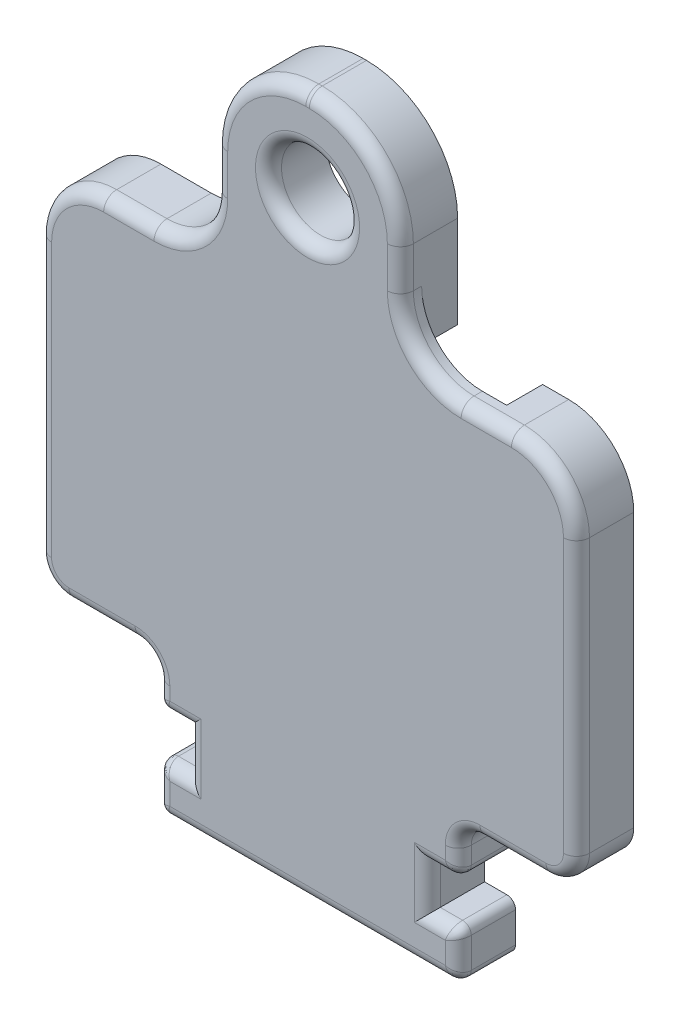
SolidWorks part; units mm, degrees
ref_plane "Front Plane" through (0, 0, 0) normal (0, 0, 1) x (1, 0, 0)
ref_plane "Top Plane" through (0, 0, 0) normal (0, 1, 0) x (1, 0, 0)
ref_plane "Right Plane" through (0, 0, 0) normal (1, 0, 0) x (0, 0, -1)
sketch "Sketch1" plane through (0, 0, 0) normal (0, 0, 1) x (1, 0, 0)
  line L0 (-8.8265, -16.637) -> (-8.8265, -18.415)
  line L1 (-11.938, 10.795) -> (-8.9916, 10.795)
  line L2 (-15.748, 6.985) -> (-15.748, -9.017)
  line L3 (-13.97, -10.795) -> (-10.0965, -10.795)
  line L4 (-8.3185, -13.589) -> (-7.0104, -13.589)
  line L5 (8.8265, -12.065) -> (8.8265, -13.081)
  line L6 (0, 22.0726) -> (0, -18.923) construction
  line L7 (-0.1016, 22.0726) -> (0.1016, 22.0726)
  line L8 (-5.4356, 16.7386) -> (-5.4356, 14.351)
  line L9 (-8.3185, -16.129) -> (-7.0104, -16.129)
  line L10 (-7.0104, -13.589) -> (-7.0104, -16.129)
  line L11 (7.0104, -13.589) -> (7.0104, -16.129)
  line L12 (8.3185, -16.129) -> (7.0104, -16.129)
  line L13 (5.4356, 16.7386) -> (5.4356, 14.351)
  line L14 (-8.8265, -12.065) -> (-8.8265, -13.081)
  line L15 (-8.3185, -18.923) -> (8.3185, -18.923)
  line L16 (8.3185, -13.589) -> (7.0104, -13.589)
  line L17 (13.97, -10.795) -> (10.0965, -10.795)
  line L18 (15.748, 6.985) -> (15.748, -9.017)
  line L19 (11.938, 10.795) -> (8.9916, 10.795)
  line L20 (8.8265, -16.637) -> (8.8265, -18.415)
  arc A0 (-0.1016, 22.0726) -> (-5.4356, 16.7386) centre (-0.1016, 16.7386) ccw
  arc A1 (-5.4356, 14.351) -> (-8.9916, 10.795) centre (-8.9916, 14.351) cw
  arc A2 (-11.938, 10.795) -> (-15.748, 6.985) centre (-11.938, 6.985) ccw
  arc A3 (-15.748, -9.017) -> (-13.97, -10.795) centre (-13.97, -9.017) ccw
  arc A4 (-8.8265, -12.065) -> (-10.0965, -10.795) centre (-10.0965, -12.065) ccw
  arc A5 (-8.3185, -13.589) -> (-8.8265, -13.081) centre (-8.3185, -13.081) cw
  arc A6 (-8.3185, -16.129) -> (-8.8265, -16.637) centre (-8.3185, -16.637) ccw
  arc A7 (-8.8265, -18.415) -> (-8.3185, -18.923) centre (-8.3185, -18.415) ccw
  circle A8 centre (0, 16.7386) radius 2.286
  arc A9 (8.8265, -18.415) -> (8.3185, -18.923) centre (8.3185, -18.415) cw
  arc A10 (8.3185, -16.129) -> (8.8265, -16.637) centre (8.3185, -16.637) cw
  arc A11 (8.3185, -13.589) -> (8.8265, -13.081) centre (8.3185, -13.081) ccw
  arc A12 (8.8265, -12.065) -> (10.0965, -10.795) centre (10.0965, -12.065) cw
  arc A13 (15.748, -9.017) -> (13.97, -10.795) centre (13.97, -9.017) cw
  arc A14 (11.938, 10.795) -> (15.748, 6.985) centre (11.938, 6.985) cw
  arc A15 (5.4356, 14.351) -> (8.9916, 10.795) centre (8.9916, 14.351) ccw
  arc A16 (0.1016, 22.0726) -> (5.4356, 16.7386) centre (0.1016, 16.7386) cw
  point P0 (0, 0)
  point P1 (-8.8265, -14.859)
  point P6 (0, 10.795)
  point P11 (0, -10.795)
  point P17 (-7.0104, -14.859)
  point P20 (-5.4356, 22.0726)
  point P23 (-5.4356, 10.795)
  point P26 (-15.748, 10.795)
  point P29 (-15.748, -10.795)
  point P32 (-8.8265, -10.795)
  point P37 (-8.8265, -16.129)
  point P40 (-8.8265, -18.923)
  point P67 (8.8265, -14.859)
  point P70 (0, 1.5748)
  dimension "D9" = 5.334
  dimension "D10" = 3.556
  dimension "D11" = 3.81
  dimension "D12" = 1.778
  dimension "D13" = 1.27
  dimension "D14" = 0.508
  dimension "D15" = 0.508
  dimension "D16" = 0.508
  dimension "D17" = 5.334
  dimension "D1" = 8.8265
  dimension "D2" = 5.4356
  dimension "D3" = 15.748
  dimension "D4" = 11.2776
  dimension "D5" = 21.59
  dimension "D6" = 8.128
  dimension "D7" = 6.9215
  dimension "D8" = 7.0104
extrude "Boss-Extrude1" add sketch "Sketch1" along normal blind 3.3528
fillet "Fillet3" radius 0.762 37 edges at (2.286, 16.7386, 3.3528) (-7.6645, -13.589, 3.3528) (-8.6777, -13.4402, 3.3528) (-8.8265, -12.573, 3.3528) (-9.1985, -11.167, 3.3528) (-12.0333, -10.795, 3.3528) (-15.2272, -10.2742, 3.3528) (-15.748, -1.016, 3.3528) (-14.6321, 9.6791, 3.3528) (-10.4648, 10.795, 3.3528) (-6.4771, 11.8365, 3.3528) (-5.4356, 15.5448, 3.3528) (-3.8733, 20.5103, 3.3528) (0, 22.0726, 3.3528) (3.8733, 20.5103, 3.3528) (5.4356, 15.5448, 3.3528) (6.4771, 11.8365, 3.3528) (10.4648, 10.795, 3.3528) (14.6321, 9.6791, 3.3528) (15.748, -1.016, 3.3528) (15.2272, -10.2742, 3.3528) (12.0333, -10.795, 3.3528) (9.1985, -11.167, 3.3528) (8.8265, -12.573, 3.3528) (8.6777, -13.4402, 3.3528) (7.6644, -13.589, 3.3528) (7.0104, -14.859, 3.3528) (7.6644, -16.129, 3.3528) (8.6777, -16.2778, 3.3528) (8.8265, -17.526, 3.3528) (8.6777, -18.7742, 3.3528) (0, -18.923, 3.3528) (-8.6777, -18.7742, 3.3528) (-8.8265, -17.526, 3.3528) (-8.6777, -16.2778, 3.3528) (-7.6644, -16.129, 3.3528) (-7.0104, -14.859, 3.3528)
sketch "Sketch2" plane through (0, 0, 0) normal (0, 0, 1) x (1, 0, 0)
  line L1 (12.065, 10.16) -> (-12.065, 10.16)
  line L2 (14.605, 7.62) -> (14.605, -10.16)
  line L3 (14.605, -10.16) -> (6.9596, -10.16)
  line L4 (-14.605, 7.62) -> (-14.605, -10.16)
  line L5 (14.605, 10.16) -> (13.7216, 9.5454) construction
  line L8 (6.9596, -10.16) -> (6.9596, -17.78)
  line L9 (6.9596, -17.78) -> (-6.9596, -17.78)
  line L10 (-6.9596, -10.16) -> (-6.9596, -17.78)
  line L13 (-6.9596, -10.16) -> (-14.605, -10.16)
  line L14 (-13.7216, 9.5454) -> (-14.605, 10.16) construction
  arc A0 (-12.065, 10.16) -> (-14.605, 7.62) centre (-12.065, 7.62) ccw
  arc A1 (12.065, 10.16) -> (14.605, 7.62) centre (12.065, 7.62) cw
  point P0 (0, 0)
  point P12 (0, -10.16)
  dimension "D1" = 2.54
  dimension "D2" = 2.54
extrude "Cut-Extrude1" cut sketch "Sketch2" against normal blind 3.3528 and the other way blind 2.54
sketch "Sketch3" plane through (0, 0, 0) normal (0, 0, -1) x (-1, 0, 0)
  line L0 (-6.9596, -17.78) -> (6.9596, -17.78) construction
  line L1 (-6.9596, -16.637) -> (6.9596, -16.637)
  line L2 (-6.9596, -16.637) -> (-6.9596, -18.923)
  line L3 (-6.9596, -18.923) -> (6.9596, -18.923)
  line L4 (6.9596, -16.637) -> (6.9596, -18.923)
  line L5 (-6.9596, -16.637) -> (6.9596, -18.923) construction
  line L6 (-6.9596, -18.923) -> (6.9596, -16.637) construction
  line L7 (8.3185, -18.923) -> (-8.3185, -18.923) construction
  point P0 (0, -17.78)
extrude "Cut-Extrude3" cut sketch "Sketch3" against normal blind 0.5588
sketch "Sketch4" plane through (0, 0, 0) normal (0, 0, -1) x (-1, 0, 0)
  line L0 (0, 0) -> (0, 23.8191) construction
  line L2 (-5.4356, 11.3371) -> (-3.175, 11.3371)
  line L3 (-10.414, 11.3371) -> (-10.414, 9.0912)
  line L4 (-10.414, 9.0912) -> (-3.175, 9.0912)
  line L5 (-3.175, 11.3371) -> (-3.175, 9.0912)
  line L6 (-5.4356, 14.351) -> (-10.414, 14.351)
  line L7 (-5.4356, 14.351) -> (-5.4356, 11.3371)
  line L9 (-10.414, 14.351) -> (-10.414, 11.3371)
  arc A0 (-8.9916, 10.795) -> (-5.4356, 14.351) centre (-8.9916, 14.351) ccw construction
  dimension "D1" = 10.414
  dimension "D2" = 7.239
extrude "Cut-Extrude4" cut sketch "Sketch4" against normal blind 2.1082
